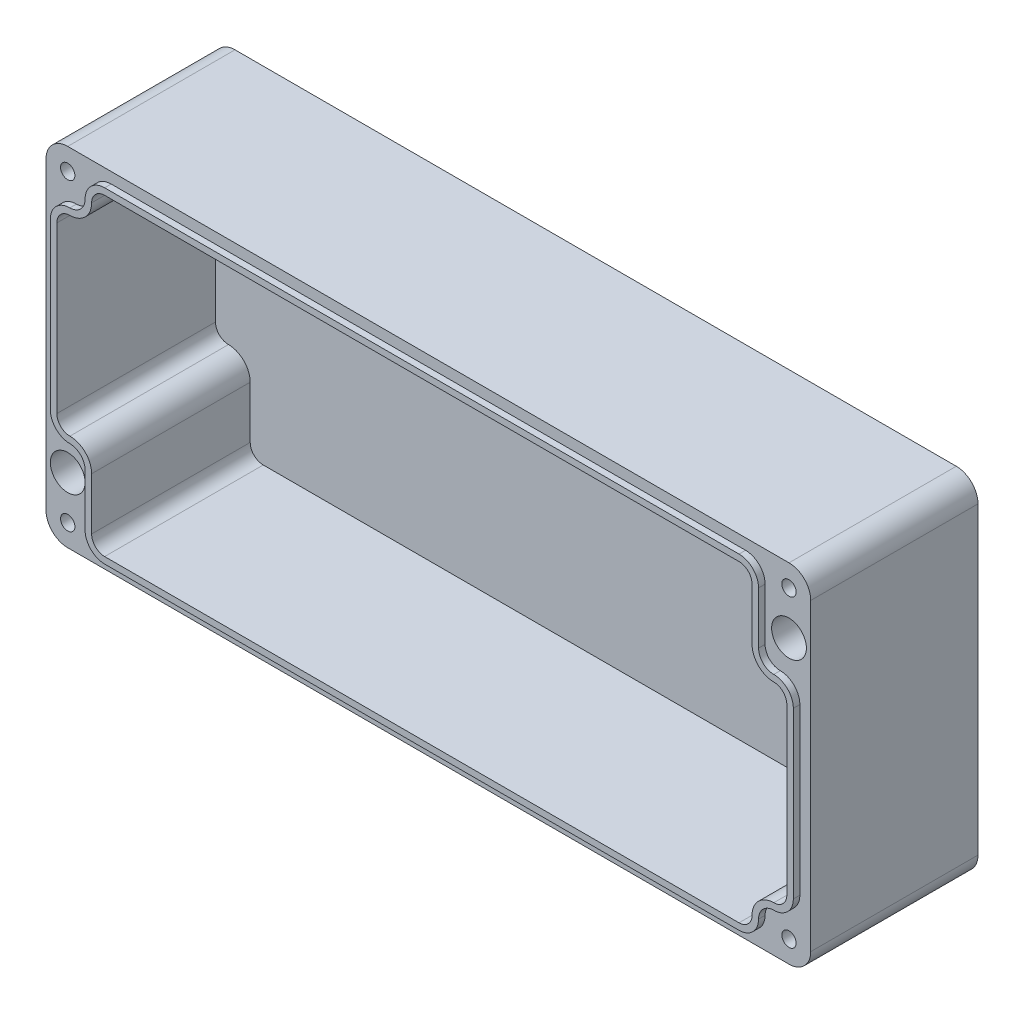
SolidWorks part; units mm, degrees
material "ألمنيوم خلائطي"
ref_plane "Front" through (0, 0, 0) normal (0, 0, 1) x (1, 0, 0)
ref_plane "Top" through (0, 0, 0) normal (0, 1, 0) x (1, 0, 0)
ref_plane "Right" through (0, 0, 0) normal (1, 0, 0) x (0, 0, -1)
sketch "Sketch1" plane through (0, 0, 0) normal (0, 0, 1) x (1, 0, 0)
  line L0 (88, 40) -> (-88, -40) construction
  line L1 (-88, 40) -> (88, 40)
  line L2 (-88, 40) -> (-88, -40)
  line L3 (-88, -40) -> (88, -40)
  line L4 (88, 40) -> (88, -40)
  dimension "D1" = 176
  dimension "D2" = 80
extrude "Boss-Extrude1" add sketch "Sketch1" along normal blind 38.5
sketch "Sketch2" plane through (0, 0, 38.5) normal (0, 0, 1) x (1, 0, 0)
  line L8 (-84, 36) -> (-84, -36)
  line L9 (-84, -36) -> (84, -36)
  line L10 (84, -36) -> (84, 36)
  line L11 (84, 36) -> (-84, 36)
  line L12 (-84, 36) -> (-84, -36)
  line L13 (-84, -36) -> (84, -36)
  line L14 (84, -36) -> (84, 36)
  line L15 (84, 36) -> (-84, 36)
  dimension "D1" = 4
extrude "Cut-Extrude1" cut sketch "Sketch2" against normal blind 35
fillet "Fillet2" radius 5 4 edges at (88, 40, 19.25) (88, -40, 19.25) (-88, -40, 19.25) (-88, 40, 19.25)
sketch "Sketch8" plane through (0, 0, 3.5) normal (0, 0, 1) x (1, 0, 0)
  line L0 (84, 36) -> (-84, 36) construction
  line L1 (76, 36) -> (84, 36)
  line L2 (76, 36) -> (76, 16)
  line L3 (76, 16) -> (84, 16)
  line L4 (84, 36) -> (84, 16)
  line L5 (84, -36) -> (84, 36) construction
  line L6 (-84, -36) -> (84, -36) construction
  line L7 (84, -28) -> (76, -28)
  line L8 (84, -28) -> (84, -36)
  line L9 (84, -36) -> (76, -36)
  line L10 (76, -28) -> (76, -36)
  line L11 (-84, 36) -> (-84, -36) construction
  line L12 (-76, -36) -> (-84, -36)
  line L13 (-76, -36) -> (-76, -16)
  line L14 (-76, -16) -> (-84, -16)
  line L15 (-84, -36) -> (-84, -16)
  line L16 (88, -35) -> (88, 35) construction
  line L17 (-84, 28) -> (-76, 28)
  line L18 (-84, 28) -> (-84, 36)
  line L19 (-84, 36) -> (-76, 36)
  line L20 (-76, 28) -> (-76, 36)
  dimension "D1" = 12
  dimension "D2" = 20
extrude "Boss-Extrude2" add sketch "Sketch8" along normal up to surface (35 mm away) up to face at (0, 0, 38.5)
fillet "Fillet4" radius 3 8 edges at (-76, 36, 21) (84, -28, 21) (76, -36, 21) (-76, -36, 21) (-84, -16, 21) (-84, 28, 21) (84, 16, 21) (76, 36, 21)
fillet "Fillet5" radius 5 4 edges at (-76, -16, 21) (76, -28, 21) (76, 16, 21) (-76, 28, 21)
hole_wizard "M4 Tapped Hole1" positions "Sketch5" profile "Sketch4" tap size "M4" standard "ISO"
sketch "Sketch5" plane through (0, 0, 38.5) normal (0, 0, 1) x (1, 0, 0)
  line L0 (-83, 35) -> (83, 35) construction
  line L1 (83, 35) -> (83, -35) construction
  line L2 (83, -35) -> (-83, -35) construction
  line L3 (-83, -35) -> (-83, 35) construction
  line L5 (-83, -35) -> (83, 35) construction
  line L7 (88, -35) -> (88, 35) construction
  line L8 (83, 40) -> (-83, 40) construction
  point P1 (-83, -35)
  point P5 (83, 35)
  point P33 (-83, 35)
  point P35 (83, -35)
  dimension "D1" = 5
  dimension "D2" = 5
sketch "Sketch4" plane through (-83, -35, 38.5) normal (1, 0, 0) x (0, -1, 0)
  line L0 (0, 0) -> (0, 12.4914)
  line L1 (0, 12.4914) -> (1.65, 11.5)
  line L2 (1.65, 11.5) -> (1.65, 0)
  line L5 (1.65, 0) -> (0, 0)
  line L10 (0, 12.4914) -> (-1.65, 11.5) construction
  line L11 (0, -6.35) -> (0, 107.95) construction
  dimension "Tap Drill Dia." = 3.3
  dimension "Tap Drill Depth" = 11.5
  dimension "Drill Angle" = 118
cosmetic thread "Hole Thread1" parameters "D1"=8, "D2"=4
cosmetic thread "Hole Thread2" parameters "D1"=8, "D2"=4
cosmetic thread "Hole Thread3" parameters "D1"=8, "D2"=4
cosmetic thread "Hole Thread4" parameters "D1"=8, "D2"=4
sketch "Sketch9" plane through (0, 0, 38.5) normal (0, 0, 1) x (1, 0, 0)
  line L0 (73, 37.5) -> (-73, 37.5)
  line L1 (-85.5, 25) -> (-85.5, -13)
  line L2 (-77.5, -21) -> (-77.5, -33)
  line L3 (-73, -37.5) -> (73, -37.5)
  line L4 (85.5, -25) -> (85.5, 13)
  line L5 (77.5, 21) -> (77.5, 33)
  line L6 (73, 36) -> (-73, 36)
  line L7 (-84, 25) -> (-84, -13)
  line L8 (-76, -21) -> (-76, -33)
  line L9 (-73, -36) -> (73, -36)
  line L10 (84, -25) -> (84, 13)
  line L11 (76, 21) -> (76, 33)
  line L12 (73, 36) -> (-73, 36)
  line L13 (-84, 25) -> (-84, -13)
  line L14 (-76, -21) -> (-76, -33)
  line L15 (-73, -36) -> (73, -36)
  line L16 (84, -25) -> (84, 13)
  line L17 (76, 21) -> (76, 33)
  arc A0 (-73, 37.5) -> (-77.5, 33) centre (-73, 33) ccw
  arc A1 (-81, 29.5) -> (-77.5, 33) centre (-81, 33) ccw
  arc A2 (-81, 29.5) -> (-85.5, 25) centre (-81, 25) ccw
  arc A3 (-85.5, -13) -> (-81, -17.5) centre (-81, -13) ccw
  arc A4 (-77.5, -21) -> (-81, -17.5) centre (-81, -21) ccw
  arc A5 (-77.5, -33) -> (-73, -37.5) centre (-73, -33) ccw
  arc A6 (73, -37.5) -> (77.5, -33) centre (73, -33) ccw
  arc A7 (81, -29.5) -> (77.5, -33) centre (81, -33) ccw
  arc A8 (81, -29.5) -> (85.5, -25) centre (81, -25) ccw
  arc A9 (85.5, 13) -> (81, 17.5) centre (81, 13) ccw
  arc A10 (77.5, 21) -> (81, 17.5) centre (81, 21) ccw
  arc A11 (77.5, 33) -> (73, 37.5) centre (73, 33) ccw
  arc A12 (-73, 36) -> (-76, 33) centre (-73, 33) ccw
  arc A13 (-81, 28) -> (-76, 33) centre (-81, 33) ccw
  arc A14 (-81, 28) -> (-84, 25) centre (-81, 25) ccw
  arc A15 (-84, -13) -> (-81, -16) centre (-81, -13) ccw
  arc A16 (-76, -21) -> (-81, -16) centre (-81, -21) ccw
  arc A17 (-76, -33) -> (-73, -36) centre (-73, -33) ccw
  arc A18 (73, -36) -> (76, -33) centre (73, -33) ccw
  arc A19 (81, -28) -> (76, -33) centre (81, -33) ccw
  arc A20 (81, -28) -> (84, -25) centre (81, -25) ccw
  arc A21 (84, 13) -> (81, 16) centre (81, 13) ccw
  arc A22 (76, 21) -> (81, 16) centre (81, 21) ccw
  arc A23 (76, 33) -> (73, 36) centre (73, 33) ccw
  arc A24 (-73, 36) -> (-76, 33) centre (-73, 33) ccw
  arc A25 (-81, 28) -> (-76, 33) centre (-81, 33) ccw
  arc A26 (-81, 28) -> (-84, 25) centre (-81, 25) ccw
  arc A27 (-84, -13) -> (-81, -16) centre (-81, -13) ccw
  arc A28 (-76, -21) -> (-81, -16) centre (-81, -21) ccw
  arc A29 (-76, -33) -> (-73, -36) centre (-73, -33) ccw
  arc A30 (73, -36) -> (76, -33) centre (73, -33) ccw
  arc A31 (81, -28) -> (76, -33) centre (81, -33) ccw
  arc A32 (81, -28) -> (84, -25) centre (81, -25) ccw
  arc A33 (84, 13) -> (81, 16) centre (81, 13) ccw
  arc A34 (76, 21) -> (81, 16) centre (81, 21) ccw
  arc A35 (76, 33) -> (73, 36) centre (73, 33) ccw
  dimension "D1" = 0
  dimension "D2" = 1.5
extrude "Boss-Extrude3" add sketch "Sketch9" along normal blind 1.5
sketch "Sketch11" plane through (0, 0, 0) normal (0, 0, -1) x (-1, 0, 0)
  line L0 (0, 40) -> (0, 0) construction
  line L1 (-83, 40) -> (83, 40) construction
hole_wizard "CBORE for M4 Cheese Head Screw1" positions "Sketch15" profile "Sketch14" counterbore size "M4" standard "ISO" end condition through all
sketch "Sketch15" plane through (0, 0, 38.5) normal (0, 0, 1) x (1, 0, 0)
  line L0 (83, 25) -> (-83, -25) construction
  line L2 (-83, -35) -> (-83, -25) construction
  point P0 (83, 25)
  point P1 (-83, -25)
  dimension "D1" = 10
sketch "Sketch14" plane through (83, 25, 38.5) normal (1, 0, 0) x (0, -1, 0)
  line L0 (0, 0) -> (0, 38.5)
  line L1 (0, 38.5) -> (2.25, 38.5)
  line L3 (2.25, 38.5) -> (2.25, 30)
  line L4 (2.25, 30) -> (4, 30)
  line L5 (4, 30) -> (4, 0)
  line L7 (4, 0) -> (0, 0)
  line L11 (0, -6.35) -> (0, 107.95) construction
  dimension "Thru Hole Dia." = 4.5
  dimension "Thru Hole Depth" = 38.5
  dimension "C'Bore Dia." = 8
  dimension "C'Bore Depth" = 30
sketch "Sketch16" [suppressed] plane through (0, 0, 38.5) normal (0, 0, 1) x (1, 0, 0)
  line L4 (88, -35) -> (88, 35)
  line L5 (83, 40) -> (-83, 40)
  line L6 (-88, 35) -> (-88, -35)
  line L7 (-83, -40) -> (83, -40)
  line L8 (88, -35) -> (88, 35)
  line L9 (83, 40) -> (-83, 40)
  line L10 (-88, 35) -> (-88, -35)
  line L11 (-83, -40) -> (83, -40)
  arc A4 (88, 35) -> (83, 40) centre (83, 35) ccw
  arc A5 (-83, 40) -> (-88, 35) centre (-83, 35) ccw
  arc A6 (-88, -35) -> (-83, -40) centre (-83, -35) ccw
  arc A7 (83, -40) -> (88, -35) centre (83, -35) ccw
  arc A8 (88, 35) -> (83, 40) centre (83, 35) ccw
  arc A9 (-83, 40) -> (-88, 35) centre (-83, 35) ccw
  arc A10 (-88, -35) -> (-83, -40) centre (-83, -35) ccw
  arc A11 (83, -40) -> (88, -35) centre (83, -35) ccw
  dimension "D1" = 0
extrude "Boss-Extrude4" [suppressed] add sketch "Sketch16" along normal blind 15
